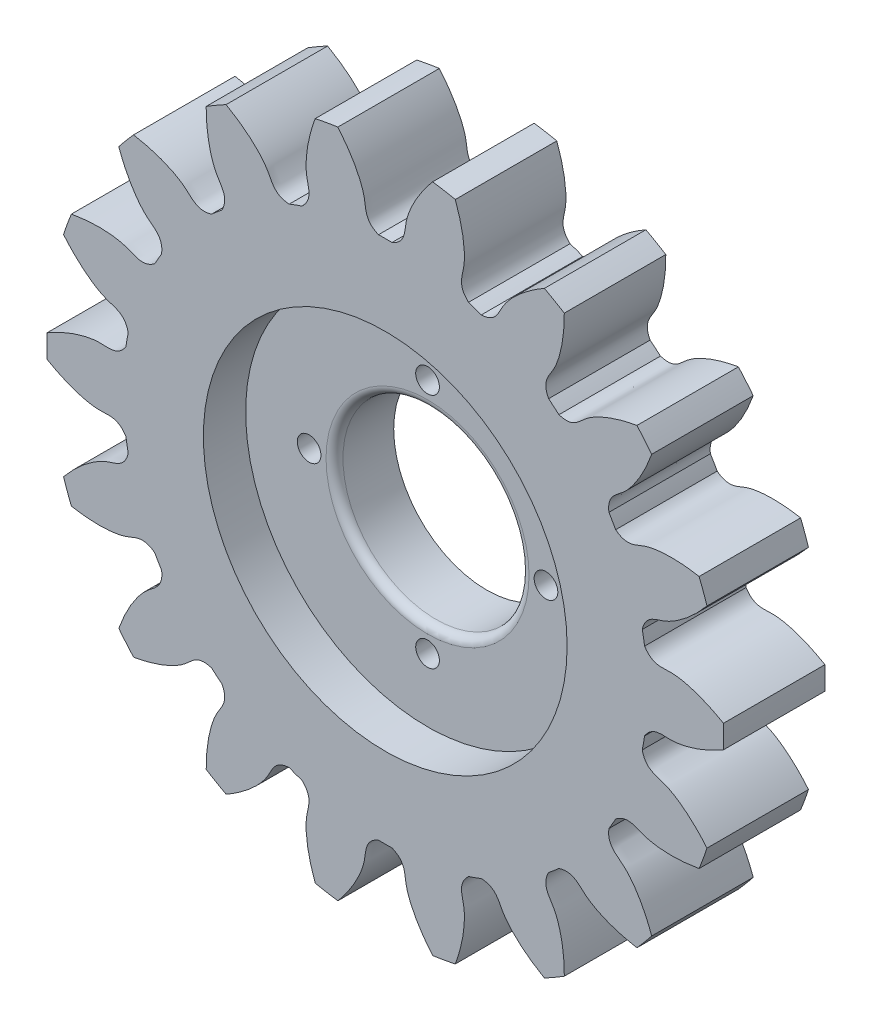
SolidWorks part; units mm, degrees
ref_plane "前视基准面" through (0, 0, 0) normal (0, 0, 1) x (1, 0, 0)
ref_plane "上视基准面" through (0, 0, 0) normal (0, 1, 0) x (1, 0, 0)
ref_plane "右视基准面" through (0, 0, 0) normal (1, 0, 0) x (0, 0, -1)
sketch "草图1" plane through (0, 0, 0) normal (0, 0, 1) x (1, 0, 0)
  circle A0 centre (0, 0) radius 20
extrude "凸台-拉伸1" add sketch "草图1" along normal blind 5
ref_axis "基准轴1" through (0, 0, -0.25) along (0, 0, 1)
sketch "草图2" plane through (0, 0, 0) normal (0, 0, 1) x (1, 0, 0)
  line L0 (0, 0) -> (0, 20) construction
  circle A0 centre (0, 0) radius 20 construction
  arc A1 (0.3988, 15.4949) -> (-0.3988, 15.4949) centre (0, 0) ccw
  arc A2 (6.1971, 22.6134) -> (-6.1971, 22.6134) centre (0, 0) ccw
  spline S0 degree 3 poles (0.3988, 15.4949) (1.2302, 15.8374) (1.1256, 16.4774) (1.2637, 17.0852) (1.2775, 17.141) (1.2942, 17.2031) (1.314, 17.2713) (1.3373, 17.3456) (1.3641, 17.4258) (1.3948, 17.5118) (1.4296, 17.6035) (1.4688, 17.7008) (1.5126, 17.8035) (1.5611, 17.9115) (1.6148, 18.0246) (1.6737, 18.1427) (1.738, 18.2655) (1.8081, 18.393) (1.8841, 18.5249) (1.9662, 18.6611) (2.0547, 18.8013) (2.1496, 18.9453) (2.2513, 19.0931) (2.3598, 19.2442) (2.4753, 19.3986) (2.5981, 19.5559) (2.7283, 19.7161) (2.866, 19.8787) (3.0115, 20.0437) (3.1648, 20.2106) (3.326, 20.3794) (3.4954, 20.5497) (3.673, 20.7213) (3.859, 20.8939) (4.0534, 21.0673) (4.2564, 21.2412) (4.468, 21.4152) (4.6884, 21.5892) (4.9177, 21.7628) (5.1558, 21.9358) (5.4029, 22.1078) (5.7482, 22.3381) (6.0151, 22.5047) (6.1971, 22.6134) knots 0 0 0 0 0.187592 0.192996 0.199121 0.205966 0.213531 0.221818 0.230824 0.240552 0.250999 0.262168 0.274057 0.286666 0.299996 0.314047 0.328818 0.344309 0.360521 0.377454 0.395107 0.413481 0.432575 0.45239 0.472926 0.494181 0.516158 0.538855 0.562272 0.58641 0.611269 0.636848 0.663148 0.690168 0.717909 0.74637 0.775552 0.805454 0.836077 0.867421 0.899485 0.932269 1 1 1 1
  spline S1 degree 3 poles (-0.3988, 15.4949) (-1.2302, 15.8374) (-1.1256, 16.4774) (-1.2637, 17.0852) (-1.2775, 17.141) (-1.2942, 17.2031) (-1.314, 17.2713) (-1.3373, 17.3456) (-1.3641, 17.4258) (-1.3948, 17.5118) (-1.4296, 17.6035) (-1.4688, 17.7008) (-1.5126, 17.8035) (-1.5611, 17.9115) (-1.6148, 18.0246) (-1.6737, 18.1427) (-1.738, 18.2655) (-1.8081, 18.393) (-1.8841, 18.5249) (-1.9662, 18.6611) (-2.0547, 18.8013) (-2.1496, 18.9453) (-2.2513, 19.0931) (-2.3598, 19.2442) (-2.4753, 19.3986) (-2.5981, 19.5559) (-2.7283, 19.7161) (-2.866, 19.8787) (-3.0115, 20.0437) (-3.1648, 20.2106) (-3.326, 20.3794) (-3.4954, 20.5497) (-3.673, 20.7213) (-3.859, 20.8939) (-4.0534, 21.0673) (-4.2564, 21.2412) (-4.468, 21.4152) (-4.6884, 21.5892) (-4.9177, 21.7628) (-5.1558, 21.9358) (-5.4029, 22.1078) (-5.7482, 22.3381) (-6.0151, 22.5047) (-6.1971, 22.6134) knots 0 0 0 0 0.187592 0.192996 0.199121 0.205966 0.213531 0.221818 0.230824 0.240552 0.250999 0.262168 0.274057 0.286666 0.299996 0.314047 0.328818 0.344309 0.360521 0.377454 0.395107 0.413481 0.432575 0.45239 0.472926 0.494181 0.516158 0.538855 0.562272 0.58641 0.611269 0.636848 0.663148 0.690168 0.717909 0.74637 0.775552 0.805454 0.836077 0.867421 0.899485 0.932269 1 1 1 1
extrude "切除-拉伸1" cut sketch "草图2" along normal through all
pattern_circular "阵列(圆周)1" count 18 every 20 about axis through (0, 0, -0.25) along (0, 0, 1) of "切除-拉伸1"
sketch "草图3" plane through (0, 0, 0) normal (0, 0, 1) x (1, 0, 0)
  circle A0 centre (0, 0) radius 18 construction
  dimension "Dn" = 36
sketch "草图4" plane through (0, 0, 5) normal (0, 0, 1) x (1, 0, 0)
  circle A0 centre (0, 0) radius 10.75
  dimension "D1" = 21.5
extrude "切除-拉伸2" cut sketch "草图4" against normal blind 2.5
sketch "草图5" plane through (0, 0, 2.5) normal (0, 0, 1) x (1, 0, 0)
  circle A0 centre (0, 0) radius 5.5
  dimension "D1" = 11
extrude "切除-拉伸3" cut sketch "草图5" against normal blind 12.5
sketch "草图7" plane through (0, 0, 0) normal (0, 0, -1) x (-1, 0, 0)
  circle A0 centre (0, 0) radius 5.5 construction
  circle A1 centre (0, 0) radius 5.5
  arc A36 (5.6743, 14.424) -> (4.9248, 14.6968) centre (0, 0) ccw
  arc A37 (4.14, 19.5668) -> (2.802, 19.8028) centre (0, 0) ccw
  arc A38 (0.3988, 15.4949) -> (-0.3988, 15.4949) centre (0, 0) ccw
  arc A39 (-2.802, 19.8028) -> (-4.14, 19.5668) centre (0, 0) ccw
  arc A40 (-4.9248, 14.6968) -> (-5.6743, 14.424) centre (0, 0) ccw
  arc A41 (-9.4059, 17.6502) -> (-10.5825, 16.9709) centre (0, 0) ccw
  arc A42 (-9.6544, 12.1261) -> (-10.2654, 11.6134) centre (0, 0) ccw
  arc A43 (-14.8754, 13.3687) -> (-15.7487, 12.3279) centre (0, 0) ccw
  arc A44 (-13.2195, 8.0928) -> (-13.6184, 7.4021) centre (0, 0) ccw
  arc A45 (-18.5507, 7.4748) -> (-19.0153, 6.1981) centre (0, 0) ccw
  arc A46 (-15.1902, 3.0834) -> (-15.3287, 2.2979) centre (0, 0) ccw
  arc A47 (-19.9885, 0.6793) -> (-19.9885, -0.6793) centre (0, 0) ccw
  arc A48 (-15.3287, -2.2979) -> (-15.1902, -3.0834) centre (0, 0) ccw
  arc A49 (-19.0153, -6.1981) -> (-18.5507, -7.4748) centre (0, 0) ccw
  arc A50 (-13.6184, -7.4021) -> (-13.2195, -8.0928) centre (0, 0) ccw
  arc A51 (-15.7487, -12.3279) -> (-14.8754, -13.3687) centre (0, 0) ccw
  arc A52 (-10.2654, -11.6134) -> (-9.6544, -12.1261) centre (0, 0) ccw
  arc A53 (-10.5825, -16.9709) -> (-9.4059, -17.6502) centre (0, 0) ccw
  arc A54 (-5.6743, -14.424) -> (-4.9248, -14.6968) centre (0, 0) ccw
  arc A55 (-4.14, -19.5668) -> (-2.802, -19.8028) centre (0, 0) ccw
  arc A56 (-0.3988, -15.4949) -> (0.3988, -15.4949) centre (0, 0) ccw
  arc A57 (2.802, -19.8028) -> (4.14, -19.5668) centre (0, 0) ccw
  arc A58 (4.9248, -14.6968) -> (5.6743, -14.424) centre (0, 0) ccw
  arc A59 (9.4059, -17.6502) -> (10.5825, -16.9709) centre (0, 0) ccw
  arc A60 (9.6544, -12.1261) -> (10.2654, -11.6134) centre (0, 0) ccw
  arc A61 (14.8754, -13.3687) -> (15.7487, -12.3279) centre (0, 0) ccw
  arc A62 (13.2195, -8.0928) -> (13.6184, -7.4021) centre (0, 0) ccw
  arc A63 (18.5507, -7.4748) -> (19.0153, -6.1981) centre (0, 0) ccw
  arc A64 (15.1902, -3.0834) -> (15.3287, -2.2979) centre (0, 0) ccw
  arc A65 (19.9885, -0.6793) -> (19.9885, 0.6793) centre (0, 0) ccw
  arc A66 (15.3287, 2.2979) -> (15.1902, 3.0834) centre (0, 0) ccw
  arc A67 (19.0153, 6.1981) -> (18.5507, 7.4748) centre (0, 0) ccw
  arc A68 (13.6184, 7.4021) -> (13.2195, 8.0928) centre (0, 0) ccw
  arc A69 (15.7487, 12.3279) -> (14.8754, 13.3687) centre (0, 0) ccw
  arc A70 (10.2654, 11.6134) -> (9.6544, 12.1261) centre (0, 0) ccw
  arc A71 (10.5825, 16.9709) -> (9.4059, 17.6502) centre (0, 0) ccw
  arc A72 (5.6743, 14.424) -> (4.9248, 14.6968) centre (0, 0) ccw
  arc A73 (4.14, 19.5668) -> (2.802, 19.8028) centre (0, 0) ccw
  arc A74 (0.3988, 15.4949) -> (-0.3988, 15.4949) centre (0, 0) ccw
  arc A75 (-2.802, 19.8028) -> (-4.14, 19.5668) centre (0, 0) ccw
  arc A76 (-4.9248, 14.6968) -> (-5.6743, 14.424) centre (0, 0) ccw
  arc A77 (-9.4059, 17.6502) -> (-10.5825, 16.9709) centre (0, 0) ccw
  arc A78 (-9.6544, 12.1261) -> (-10.2654, 11.6134) centre (0, 0) ccw
  arc A79 (-14.8754, 13.3687) -> (-15.7487, 12.3279) centre (0, 0) ccw
  arc A80 (-13.2195, 8.0928) -> (-13.6184, 7.4021) centre (0, 0) ccw
  arc A81 (-18.5507, 7.4748) -> (-19.0153, 6.1981) centre (0, 0) ccw
  arc A82 (-15.1902, 3.0834) -> (-15.3287, 2.2979) centre (0, 0) ccw
  arc A83 (-19.9885, 0.6793) -> (-19.9885, -0.6793) centre (0, 0) ccw
  arc A84 (-15.3287, -2.2979) -> (-15.1902, -3.0834) centre (0, 0) ccw
  arc A85 (-19.0153, -6.1981) -> (-18.5507, -7.4748) centre (0, 0) ccw
  arc A86 (-13.6184, -7.4021) -> (-13.2195, -8.0928) centre (0, 0) ccw
  arc A87 (-15.7487, -12.3279) -> (-14.8754, -13.3687) centre (0, 0) ccw
  arc A88 (-10.2654, -11.6134) -> (-9.6544, -12.1261) centre (0, 0) ccw
  arc A89 (-10.5825, -16.9709) -> (-9.4059, -17.6502) centre (0, 0) ccw
  arc A90 (-5.6743, -14.424) -> (-4.9248, -14.6968) centre (0, 0) ccw
  arc A91 (-4.14, -19.5668) -> (-2.802, -19.8028) centre (0, 0) ccw
  arc A92 (-0.3988, -15.4949) -> (0.3988, -15.4949) centre (0, 0) ccw
  arc A93 (2.802, -19.8028) -> (4.14, -19.5668) centre (0, 0) ccw
  arc A94 (4.9248, -14.6968) -> (5.6743, -14.424) centre (0, 0) ccw
  arc A95 (9.4059, -17.6502) -> (10.5825, -16.9709) centre (0, 0) ccw
  arc A96 (9.6544, -12.1261) -> (10.2654, -11.6134) centre (0, 0) ccw
  arc A97 (14.8754, -13.3687) -> (15.7487, -12.3279) centre (0, 0) ccw
  arc A98 (13.2195, -8.0928) -> (13.6184, -7.4021) centre (0, 0) ccw
  arc A99 (18.5507, -7.4748) -> (19.0153, -6.1981) centre (0, 0) ccw
  arc A100 (15.1902, -3.0834) -> (15.3287, -2.2979) centre (0, 0) ccw
  arc A101 (19.9885, -0.6793) -> (19.9885, 0.6793) centre (0, 0) ccw
  arc A102 (15.3287, 2.2979) -> (15.1902, 3.0834) centre (0, 0) ccw
  arc A103 (19.0153, 6.1981) -> (18.5507, 7.4748) centre (0, 0) ccw
  arc A104 (13.6184, 7.4021) -> (13.2195, 8.0928) centre (0, 0) ccw
  arc A105 (15.7487, 12.3279) -> (14.8754, 13.3687) centre (0, 0) ccw
  arc A106 (10.2654, 11.6134) -> (9.6544, 12.1261) centre (0, 0) ccw
  arc A107 (10.5825, 16.9709) -> (9.4059, 17.6502) centre (0, 0) ccw
  spline S36 degree 3 poles (-1821.1563, 823.0655) (138.0406, -70.6947) (34.3771, 34.3484) (8.6502, 17.177) (8.3656, 16.9701) (8.1106, 16.7688) (7.8845, 16.5751) (7.7151, 16.4178) (7.5666, 16.2712) (7.4606, 16.1603) (7.3642, 16.0529) (7.3001, 15.9787) (7.2418, 15.9083) (7.1891, 15.8421) (7.1419, 15.7803) (7.0886, 15.7075) (7.0425, 15.6406) (3.1814, 9.6493) (27.7855, -14.1214) (-1623.8886, 1173.6915) knots -9.275364 -9.275364 -9.275364 -9.275364 0.527074 0.567425 0.604893 0.639479 0.671182 0.700004 0.713334 0.737832 0.749001 0.759448 0.769176 0.778182 0.786469 0.794034 0.807004 0.812408 3.071148 3.071148 3.071148 3.071148 only from (9.4059, 17.6502) to (5.6743, 14.424)
  spline S37 degree 3 poles (1998.3999, -144.7152) (-30.3619, 7.0426) (3.7654, 9.4367) (4.6587, 16.5083) (4.6664, 16.5891) (4.6723, 16.6791) (4.6759, 16.7569) (4.6781, 16.8414) (4.6789, 16.9677) (4.6746, 17.1425) (4.6597, 17.3721) (4.6329, 17.6278) (4.5921, 17.9091) (4.535, 18.2151) (4.4598, 18.545) (4.3644, 18.8978) (-5.0832, 49.0019) (-152.7401, 32.5697) (1924.3252, -539.3464) knots -2.071146 -2.071146 -2.071146 -2.071146 0.187592 0.192996 0.205966 0.213531 0.221818 0.230824 0.240552 0.262168 0.286666 0.314047 0.344309 0.377454 0.413481 0.45239 0.494181 10.492028 10.492028 10.492028 10.492028 only from (4.9248, 14.6968) to (4.14, 19.5668)
  spline S38 degree 3 poles (-1992.8321, 150.5565) (153.8948, -19.2186) (20.556, 44.0346) (2.2536, 19.0996) (2.0569, 18.8079) (1.8862, 18.5315) (1.74, 18.2722) (1.6346, 18.0664) (1.5452, 17.8779) (1.4835, 17.7374) (1.4296, 17.6035) (1.3948, 17.5118) (1.3641, 17.4258) (1.3373, 17.3456) (1.314, 17.2713) (1.2889, 17.1847) (1.2684, 17.1061) (-0.3107, 10.1555) (30.9397, -3.7665) (-1927.3823, 547.5066) knots -9.275364 -9.275364 -9.275364 -9.275364 0.527074 0.567425 0.604893 0.639479 0.671182 0.700004 0.713334 0.737832 0.749001 0.759448 0.769176 0.778182 0.786469 0.794034 0.807004 0.812408 3.071148 3.071148 3.071148 3.071148 only from (2.802, 19.8028) to (0.3988, 15.4949)
  spline S39 degree 3 poles (1927.3772, 547.5052) (-30.9396, -3.7665) (0.3107, 10.1555) (-1.2684, 17.1061) (-1.2889, 17.1847) (-1.314, 17.2713) (-1.3373, 17.3456) (-1.3641, 17.4258) (-1.4066, 17.5447) (-1.4704, 17.7075) (-1.5629, 17.9181) (-1.6755, 18.1493) (-1.8102, 18.3996) (-1.9684, 18.6677) (-2.1519, 18.9519) (-2.3622, 19.2508) (-21.5363, 44.3082) (-154.6683, -21.6347) (1992.7415, 151.3382) knots -2.071146 -2.071146 -2.071146 -2.071146 0.187592 0.192996 0.205966 0.213531 0.221818 0.230824 0.240552 0.262168 0.286666 0.314047 0.344309 0.377454 0.413481 0.45239 0.494181 10.492028 10.492028 10.492028 10.492028 only from (-0.3988, 15.4949) to (-2.802, 19.8028)
  spline S40 degree 3 poles (-1924.143, -540.1119) (151.1869, 34.5755) (4.2556, 48.4096) (-4.4147, 18.7186) (-4.4998, 18.3771) (-4.5657, 18.0591) (-4.6144, 17.7653) (-4.6431, 17.5359) (-4.6626, 17.3282) (-4.6725, 17.1751) (-4.6774, 17.0309) (-4.6787, 16.9328) (-4.6781, 16.8414) (-4.6759, 16.7569) (-4.6723, 16.6791) (-4.6664, 16.5891) (-4.6587, 16.5083) (-3.7654, 9.4367) (30.362, 7.0426) (-1998.4052, -144.7156) knots -9.275364 -9.275364 -9.275364 -9.275364 0.527074 0.567425 0.604893 0.639479 0.671182 0.700004 0.713334 0.737832 0.749001 0.759448 0.769176 0.778182 0.786469 0.794034 0.807004 0.812408 3.071148 3.071148 3.071148 3.071148 only from (-4.14, 19.5668) to (-4.9248, 14.6968)
  spline S41 degree 3 poles (1623.8843, 1173.6884) (-27.7855, -14.1213) (-3.1814, 9.6493) (-7.0425, 15.6406) (-7.0886, 15.7075) (-7.1419, 15.7803) (-7.1891, 15.8421) (-7.2418, 15.9083) (-7.3224, 16.0056) (-7.438, 16.1367) (-7.597, 16.303) (-7.7819, 16.4817) (-7.994, 16.6709) (-8.2344, 16.8686) (-8.5041, 17.073) (-8.8039, 17.2819) (-35.3918, 34.2702) (-137.9411, -73.2297) (1820.8038, 823.7691) knots -2.071146 -2.071146 -2.071146 -2.071146 0.187592 0.192996 0.205966 0.213531 0.221818 0.230824 0.240552 0.262168 0.286666 0.314047 0.344309 0.377454 0.413481 0.45239 0.494181 10.492028 10.492028 10.492028 10.492028 only from (-5.6743, 14.424) to (-9.4059, 17.6502)
  spline S42 degree 3 poles (-1623.3738, -1165.6349) (130.2437, 84.1993) (-12.558, 46.9456) (-10.5506, 16.0798) (-10.5138, 15.7298) (-10.4669, 15.4084) (-10.4122, 15.1157) (-10.3607, 14.8903) (-10.308, 14.6885) (-10.2649, 14.5413) (-10.2202, 14.404) (-10.1879, 14.3114) (-10.1561, 14.2257) (-10.1251, 14.1471) (-10.0952, 14.0752) (-10.0588, 13.9927) (-10.0239, 13.9193) (-6.7658, 7.5798) (26.1222, 17.0023) (-1828.391, -819.483) knots -9.275364 -9.275364 -9.275364 -9.275364 0.527074 0.567425 0.604893 0.639479 0.671182 0.700004 0.713334 0.737832 0.749001 0.759448 0.769176 0.778182 0.786469 0.794034 0.807004 0.812408 3.071148 3.071148 3.071148 3.071148 only from (-10.5825, 16.9709) to (-9.6544, 12.1261)
  spline S43 degree 3 poles (1124.527, 1658.3075) (-21.28, -22.7729) (-6.2898, 7.9793) (-11.9672, 12.2887) (-12.0334, 12.3358) (-12.1084, 12.3859) (-12.1739, 12.4279) (-12.246, 12.4721) (-12.355, 12.5359) (-12.5085, 12.6196) (-12.7148, 12.7215) (-12.9497, 12.8262) (-13.2137, 12.9314) (-13.5072, 13.035) (-13.8306, 13.1348) (-14.1837, 13.2285) (-44.9785, 20.0988) (-104.5762, -115.992) (1429.2502, 1396.8413) knots -2.071146 -2.071146 -2.071146 -2.071146 0.187592 0.192996 0.205966 0.213531 0.221818 0.230824 0.240552 0.262168 0.286666 0.314047 0.344309 0.377454 0.413481 0.45239 0.494181 10.492028 10.492028 10.492028 10.492028 only from (-10.2654, 11.6134) to (-14.8754, 13.3687)
  spline S44 degree 3 poles (-1126.8018, -1650.565) (93.5912, 123.6675) (-27.857, 39.8193) (-15.414, 11.5015) (-15.2596, 11.1853) (-15.1057, 10.8993) (-14.9542, 10.643) (-14.8287, 10.4488) (-14.7101, 10.2771) (-14.6193, 10.1535) (-14.5303, 10.0399) (-14.4683, 9.9638) (-14.4091, 9.8942) (-14.3531, 9.8309) (-14.3004, 9.7737) (-14.2379, 9.7085) (-14.1801, 9.6515) (-8.9503, 4.8086) (18.7317, 24.9113) (-1437.8458, -1395.4087) knots -9.275364 -9.275364 -9.275364 -9.275364 0.527074 0.567425 0.604893 0.639479 0.671182 0.700004 0.713334 0.737832 0.749001 0.759448 0.769176 0.778182 0.786469 0.794034 0.807004 0.812408 3.071148 3.071148 3.071148 3.071148 only from (-15.7487, 12.3279) to (-13.2195, 8.0928)
  spline S45 degree 3 poles (489.5352, 1942.9102) (-12.2079, -28.6777) (-8.6395, 5.3468) (-15.4485, 7.4546) (-15.5268, 7.4761) (-15.6144, 7.4977) (-15.6903, 7.5147) (-15.7732, 7.5315) (-15.8975, 7.5543) (-16.0703, 7.5803) (-16.299, 7.6056) (-16.5555, 7.6236) (-16.8396, 7.6322) (-17.1509, 7.6291) (-17.4888, 7.6123) (-17.8528, 7.5796) (-49.1401, 3.5031) (-58.5979, -144.764) (865.308, 1801.4338) knots -2.071146 -2.071146 -2.071146 -2.071146 0.187592 0.192996 0.205966 0.213531 0.221818 0.230824 0.240552 0.262168 0.286666 0.314047 0.344309 0.377454 0.413481 0.45239 0.494181 10.492028 10.492028 10.492028 10.492028 only from (-13.6184, 7.4021) to (-18.5507, 7.4748)
  spline S46 degree 3 poles (-494.3208, -1936.4127) (45.6502, 148.2195) (-39.7961, 27.8903) (-18.4181, 5.536) (-18.165, 5.2916) (-17.9224, 5.0755) (-17.6924, 4.8865) (-17.5081, 4.7469) (-17.3379, 4.6262) (-17.2103, 4.5411) (-17.0878, 4.4647) (-17.0036, 4.4145) (-16.9242, 4.3693) (-16.8498, 4.329) (-16.7807, 4.2932) (-16.6998, 4.2534) (-16.6259, 4.2196) (-10.0551, 1.4575) (9.0819, 29.8156) (-873.8752, -1803.0275) knots -9.275364 -9.275364 -9.275364 -9.275364 0.527074 0.567425 0.604893 0.639479 0.671182 0.700004 0.713334 0.737832 0.749001 0.759448 0.769176 0.778182 0.786469 0.794034 0.807004 0.812408 3.071148 3.071148 3.071148 3.071148 only from (-19.0153, 6.1981) to (-15.1902, 3.0834)
  spline S47 degree 3 poles (-204.5019, 1993.1693) (-1.6633, -31.1236) (-9.9472, 2.0695) (-17.0665, 1.7213) (-17.1474, 1.7148) (-17.2371, 1.705) (-17.3143, 1.6951) (-17.3979, 1.6826) (-17.5224, 1.6614) (-17.6938, 1.6268) (-17.9173, 1.5723) (-18.1645, 1.5015) (-18.4344, 1.4124) (-18.7259, 1.3031) (-19.0377, 1.1717) (-19.3685, 1.0165) (-47.3748, -13.5151) (-5.5518, -156.0753) (196.9969, 1988.7469) knots -2.071146 -2.071146 -2.071146 -2.071146 0.187592 0.192996 0.205966 0.213531 0.221818 0.230824 0.240552 0.262168 0.286666 0.314047 0.344309 0.377454 0.413481 0.45239 0.494181 10.492028 10.492028 10.492028 10.492028 only from (-15.3287, 2.2979) to (-19.9885, 0.6793)
  spline S48 degree 3 poles (197.7825, -1988.7004) (-7.7969, 154.8941) (-46.9351, 12.5972) (-19.2008, -1.0972) (-18.8793, -1.2403) (-18.5775, -1.3604) (-18.2967, -1.4594) (-18.0758, -1.5275) (-17.8746, -1.5827) (-17.7256, -1.6191) (-17.5843, -1.6489) (-17.488, -1.6673) (-17.3979, -1.6826) (-17.3143, -1.6951) (-17.2371, -1.705) (-17.1474, -1.7148) (-17.0665, -1.7213) (-9.9472, -2.0695) (-1.6633, 31.1237) (-204.5024, -1993.1745) knots -9.275364 -9.275364 -9.275364 -9.275364 0.527074 0.567425 0.604893 0.639479 0.671182 0.700004 0.713334 0.737832 0.749001 0.759448 0.769176 0.778182 0.786469 0.794034 0.807004 0.812408 3.071148 3.071148 3.071148 3.071148 only from (-19.9885, -0.6793) to (-15.3287, -2.2979)
  spline S49 degree 3 poles (-873.8729, 1803.0227) (9.0819, -29.8155) (-10.0551, -1.4575) (-16.6259, -4.2196) (-16.6998, -4.2534) (-16.7807, -4.2932) (-16.8498, -4.329) (-16.9242, -4.3693) (-17.0339, -4.4318) (-17.1831, -4.5229) (-17.3745, -4.6506) (-17.5826, -4.8017) (-17.8058, -4.9777) (-18.0423, -5.1801) (-18.2903, -5.4102) (-18.5481, -5.6692) (-39.8953, -28.9031) (48.1639, -148.5617) (-495.0749, 1936.1877) knots -2.071146 -2.071146 -2.071146 -2.071146 0.187592 0.192996 0.205966 0.213531 0.221818 0.230824 0.240552 0.262168 0.286666 0.314047 0.344309 0.377454 0.413481 0.45239 0.494181 10.492028 10.492028 10.492028 10.492028 only from (-15.1902, -3.0834) to (-19.0153, -6.1981)
  spline S50 degree 3 poles (866.0303, -1801.1215) (-60.3036, 142.8861) (-48.4131, -4.2152) (-17.6676, -7.5981) (-17.3166, -7.6226) (-16.9919, -7.6322) (-16.6941, -7.6292) (-16.4632, -7.6176) (-16.2553, -7.6008) (-16.1028, -7.5839) (-15.9599, -7.5637) (-15.8631, -7.548) (-15.7732, -7.5315) (-15.6903, -7.5147) (-15.6144, -7.4977) (-15.5268, -7.4761) (-15.4485, -7.4546) (-8.6395, -5.3468) (-12.2079, 28.6778) (489.5365, -1942.9153) knots -9.275364 -9.275364 -9.275364 -9.275364 0.527074 0.567425 0.604893 0.639479 0.671182 0.700004 0.713334 0.737832 0.749001 0.759448 0.769176 0.778182 0.786469 0.794034 0.807004 0.812408 3.071148 3.071148 3.071148 3.071148 only from (-18.5507, -7.4748) to (-13.6184, -7.4021)
  spline S51 degree 3 poles (-1437.842, 1395.405) (18.7317, -24.9112) (-8.9503, -4.8086) (-14.1801, -9.6515) (-14.2379, -9.7085) (-14.3004, -9.7737) (-14.3531, -9.8309) (-14.4091, -9.8942) (-14.4909, -9.9905) (-14.5999, -10.1271) (-14.7361, -10.3126) (-14.88, -10.5257) (-15.0295, -10.7675) (-15.1825, -11.0385) (-15.3369, -11.3396) (-15.4906, -11.6712) (-27.6039, -40.805) (96.0703, -123.1293) (-1127.4334, 1650.0957) knots -2.071146 -2.071146 -2.071146 -2.071146 0.187592 0.192996 0.205966 0.213531 0.221818 0.230824 0.240552 0.262168 0.286666 0.314047 0.344309 0.377454 0.413481 0.45239 0.494181 10.492028 10.492028 10.492028 10.492028 only from (-13.2195, -8.0928) to (-15.7487, -12.3279)
  spline S52 degree 3 poles (1429.8221, -1396.3007) (-105.5367, 113.644) (-44.0517, -20.5193) (-14.0034, -13.1826) (-13.6652, -13.0855) (-13.3568, -12.9835) (-13.078, -12.8788) (-12.865, -12.789) (-12.6754, -12.702) (-12.5378, -12.6341) (-12.4105, -12.5661) (-12.3248, -12.5183) (-12.246, -12.4721) (-12.1739, -12.4279) (-12.1084, -12.3859) (-12.0334, -12.3358) (-11.9672, -12.2887) (-6.2898, -7.9793) (-21.2801, 22.773) (1124.53, -1658.3119) knots -9.275364 -9.275364 -9.275364 -9.275364 0.527074 0.567425 0.604893 0.639479 0.671182 0.700004 0.713334 0.737832 0.749001 0.759448 0.769176 0.778182 0.786469 0.794034 0.807004 0.812408 3.071148 3.071148 3.071148 3.071148 only from (-14.8754, -13.3687) to (-10.2654, -11.6134)
  spline S53 degree 3 poles (-1828.3862, 819.4808) (26.1222, -17.0023) (-6.7659, -7.5798) (-10.0239, -13.9193) (-10.0588, -13.9927) (-10.0952, -14.0752) (-10.1251, -14.1471) (-10.1561, -14.2257) (-10.2, -14.3442) (-10.2558, -14.5099) (-10.3203, -14.7307) (-10.3826, -14.9802) (-10.4404, -15.2585) (-10.4915, -15.5655) (-10.5336, -15.9013) (-10.5646, -16.2654) (-11.983, -47.7853) (132.3893, -82.8457) (-1623.8068, 1164.9778) knots -2.071146 -2.071146 -2.071146 -2.071146 0.187592 0.192996 0.205966 0.213531 0.221818 0.230824 0.240552 0.262168 0.286666 0.314047 0.344309 0.377454 0.413481 0.45239 0.494181 10.492028 10.492028 10.492028 10.492028 only from (-9.6544, -12.1261) to (-10.5825, -16.9709)
  spline S54 degree 3 poles (1821.1563, -823.0655) (-138.0406, 70.6947) (-34.3771, -34.3484) (-8.6502, -17.177) (-8.3656, -16.9701) (-8.1106, -16.7688) (-7.8845, -16.5751) (-7.7151, -16.4178) (-7.5666, -16.2712) (-7.4606, -16.1603) (-7.3642, -16.0529) (-7.3001, -15.9787) (-7.2418, -15.9083) (-7.1891, -15.8421) (-7.1419, -15.7803) (-7.0886, -15.7075) (-7.0425, -15.6406) (-3.1814, -9.6493) (-27.7855, 14.1214) (1623.8886, -1173.6915) knots -9.275364 -9.275364 -9.275364 -9.275364 0.527074 0.567425 0.604893 0.639479 0.671182 0.700004 0.713334 0.737832 0.749001 0.759448 0.769176 0.778182 0.786469 0.794034 0.807004 0.812408 3.071148 3.071148 3.071148 3.071148 only from (-9.4059, -17.6502) to (-5.6743, -14.424)
  spline S55 degree 3 poles (-1998.3999, 144.7152) (30.3619, -7.0426) (-3.7654, -9.4367) (-4.6587, -16.5083) (-4.6664, -16.5891) (-4.6723, -16.6791) (-4.6759, -16.7569) (-4.6781, -16.8414) (-4.6789, -16.9677) (-4.6746, -17.1425) (-4.6597, -17.3721) (-4.6329, -17.6278) (-4.5921, -17.9091) (-4.535, -18.2151) (-4.4598, -18.545) (-4.3644, -18.8978) (5.0832, -49.0019) (152.7401, -32.5697) (-1924.3252, 539.3464) knots -2.071146 -2.071146 -2.071146 -2.071146 0.187592 0.192996 0.205966 0.213531 0.221818 0.230824 0.240552 0.262168 0.286666 0.314047 0.344309 0.377454 0.413481 0.45239 0.494181 10.492028 10.492028 10.492028 10.492028 only from (-4.9248, -14.6968) to (-4.14, -19.5668)
  spline S56 degree 3 poles (1992.8321, -150.5565) (-153.8948, 19.2186) (-20.556, -44.0346) (-2.2536, -19.0996) (-2.0569, -18.8079) (-1.8862, -18.5315) (-1.74, -18.2722) (-1.6346, -18.0664) (-1.5452, -17.8779) (-1.4835, -17.7374) (-1.4296, -17.6035) (-1.3948, -17.5118) (-1.3641, -17.4258) (-1.3373, -17.3456) (-1.314, -17.2713) (-1.2889, -17.1847) (-1.2684, -17.1061) (0.3107, -10.1555) (-30.9397, 3.7665) (1927.3823, -547.5066) knots -9.275364 -9.275364 -9.275364 -9.275364 0.527074 0.567425 0.604893 0.639479 0.671182 0.700004 0.713334 0.737832 0.749001 0.759448 0.769176 0.778182 0.786469 0.794034 0.807004 0.812408 3.071148 3.071148 3.071148 3.071148 only from (-2.802, -19.8028) to (-0.3988, -15.4949)
  spline S57 degree 3 poles (-1927.3772, -547.5052) (30.9396, 3.7665) (-0.3107, -10.1555) (1.2684, -17.1061) (1.2889, -17.1847) (1.314, -17.2713) (1.3373, -17.3456) (1.3641, -17.4258) (1.4066, -17.5447) (1.4704, -17.7075) (1.5629, -17.9181) (1.6755, -18.1493) (1.8102, -18.3996) (1.9684, -18.6677) (2.1519, -18.9519) (2.3622, -19.2508) (21.5363, -44.3082) (154.6683, 21.6347) (-1992.7415, -151.3382) knots -2.071146 -2.071146 -2.071146 -2.071146 0.187592 0.192996 0.205966 0.213531 0.221818 0.230824 0.240552 0.262168 0.286666 0.314047 0.344309 0.377454 0.413481 0.45239 0.494181 10.492028 10.492028 10.492028 10.492028 only from (0.3988, -15.4949) to (2.802, -19.8028)
  spline S58 degree 3 poles (1924.143, 540.1119) (-151.1869, -34.5755) (-4.2556, -48.4096) (4.4147, -18.7186) (4.4998, -18.3771) (4.5657, -18.0591) (4.6144, -17.7653) (4.6431, -17.5359) (4.6626, -17.3282) (4.6725, -17.1751) (4.6774, -17.0309) (4.6787, -16.9328) (4.6781, -16.8414) (4.6759, -16.7569) (4.6723, -16.6791) (4.6664, -16.5891) (4.6587, -16.5083) (3.7654, -9.4367) (-30.362, -7.0426) (1998.4052, 144.7156) knots -9.275364 -9.275364 -9.275364 -9.275364 0.527074 0.567425 0.604893 0.639479 0.671182 0.700004 0.713334 0.737832 0.749001 0.759448 0.769176 0.778182 0.786469 0.794034 0.807004 0.812408 3.071148 3.071148 3.071148 3.071148 only from (4.14, -19.5668) to (4.9248, -14.6968)
  spline S59 degree 3 poles (-1623.8843, -1173.6884) (27.7855, 14.1213) (3.1814, -9.6493) (7.0425, -15.6406) (7.0886, -15.7075) (7.1419, -15.7803) (7.1891, -15.8421) (7.2418, -15.9083) (7.3224, -16.0056) (7.438, -16.1367) (7.597, -16.303) (7.7819, -16.4817) (7.994, -16.6709) (8.2344, -16.8686) (8.5041, -17.073) (8.8039, -17.2819) (35.3918, -34.2702) (137.9411, 73.2297) (-1820.8038, -823.7691) knots -2.071146 -2.071146 -2.071146 -2.071146 0.187592 0.192996 0.205966 0.213531 0.221818 0.230824 0.240552 0.262168 0.286666 0.314047 0.344309 0.377454 0.413481 0.45239 0.494181 10.492028 10.492028 10.492028 10.492028 only from (5.6743, -14.424) to (9.4059, -17.6502)
  spline S60 degree 3 poles (1623.3738, 1165.6349) (-130.2437, -84.1993) (12.558, -46.9456) (10.5506, -16.0798) (10.5138, -15.7298) (10.4669, -15.4084) (10.4122, -15.1157) (10.3607, -14.8903) (10.308, -14.6885) (10.2649, -14.5413) (10.2202, -14.404) (10.1879, -14.3114) (10.1561, -14.2257) (10.1251, -14.1471) (10.0952, -14.0752) (10.0588, -13.9927) (10.0239, -13.9193) (6.7658, -7.5798) (-26.1222, -17.0023) (1828.391, 819.483) knots -9.275364 -9.275364 -9.275364 -9.275364 0.527074 0.567425 0.604893 0.639479 0.671182 0.700004 0.713334 0.737832 0.749001 0.759448 0.769176 0.778182 0.786469 0.794034 0.807004 0.812408 3.071148 3.071148 3.071148 3.071148 only from (10.5825, -16.9709) to (9.6544, -12.1261)
  spline S61 degree 3 poles (-1124.527, -1658.3075) (21.28, 22.7729) (6.2898, -7.9793) (11.9672, -12.2887) (12.0334, -12.3358) (12.1084, -12.3859) (12.1739, -12.4279) (12.246, -12.4721) (12.355, -12.5359) (12.5085, -12.6196) (12.7148, -12.7215) (12.9497, -12.8262) (13.2137, -12.9314) (13.5072, -13.035) (13.8306, -13.1348) (14.1837, -13.2285) (44.9785, -20.0988) (104.5762, 115.992) (-1429.2502, -1396.8413) knots -2.071146 -2.071146 -2.071146 -2.071146 0.187592 0.192996 0.205966 0.213531 0.221818 0.230824 0.240552 0.262168 0.286666 0.314047 0.344309 0.377454 0.413481 0.45239 0.494181 10.492028 10.492028 10.492028 10.492028 only from (10.2654, -11.6134) to (14.8754, -13.3687)
  spline S62 degree 3 poles (1126.8018, 1650.565) (-93.5912, -123.6675) (27.857, -39.8193) (15.414, -11.5015) (15.2596, -11.1853) (15.1057, -10.8993) (14.9542, -10.643) (14.8287, -10.4488) (14.7101, -10.2771) (14.6193, -10.1535) (14.5303, -10.0399) (14.4683, -9.9638) (14.4091, -9.8942) (14.3531, -9.8309) (14.3004, -9.7737) (14.2379, -9.7085) (14.1801, -9.6515) (8.9503, -4.8086) (-18.7317, -24.9113) (1437.8458, 1395.4087) knots -9.275364 -9.275364 -9.275364 -9.275364 0.527074 0.567425 0.604893 0.639479 0.671182 0.700004 0.713334 0.737832 0.749001 0.759448 0.769176 0.778182 0.786469 0.794034 0.807004 0.812408 3.071148 3.071148 3.071148 3.071148 only from (15.7487, -12.3279) to (13.2195, -8.0928)
  spline S63 degree 3 poles (-489.5352, -1942.9102) (12.2079, 28.6777) (8.6395, -5.3468) (15.4485, -7.4546) (15.5268, -7.4761) (15.6144, -7.4977) (15.6903, -7.5147) (15.7732, -7.5315) (15.8975, -7.5543) (16.0703, -7.5803) (16.299, -7.6056) (16.5555, -7.6236) (16.8396, -7.6322) (17.1509, -7.6291) (17.4888, -7.6123) (17.8528, -7.5796) (49.1401, -3.5031) (58.5979, 144.764) (-865.308, -1801.4338) knots -2.071146 -2.071146 -2.071146 -2.071146 0.187592 0.192996 0.205966 0.213531 0.221818 0.230824 0.240552 0.262168 0.286666 0.314047 0.344309 0.377454 0.413481 0.45239 0.494181 10.492028 10.492028 10.492028 10.492028 only from (13.6184, -7.4021) to (18.5507, -7.4748)
  spline S64 degree 3 poles (494.3208, 1936.4127) (-45.6502, -148.2195) (39.7961, -27.8903) (18.4181, -5.536) (18.165, -5.2916) (17.9224, -5.0755) (17.6924, -4.8865) (17.5081, -4.7469) (17.3379, -4.6262) (17.2103, -4.5411) (17.0878, -4.4647) (17.0036, -4.4145) (16.9242, -4.3693) (16.8498, -4.329) (16.7807, -4.2932) (16.6998, -4.2534) (16.6259, -4.2196) (10.0551, -1.4575) (-9.0819, -29.8156) (873.8752, 1803.0275) knots -9.275364 -9.275364 -9.275364 -9.275364 0.527074 0.567425 0.604893 0.639479 0.671182 0.700004 0.713334 0.737832 0.749001 0.759448 0.769176 0.778182 0.786469 0.794034 0.807004 0.812408 3.071148 3.071148 3.071148 3.071148 only from (19.0153, -6.1981) to (15.1902, -3.0834)
  spline S65 degree 3 poles (204.5019, -1993.1693) (1.6633, 31.1236) (9.9472, -2.0695) (17.0665, -1.7213) (17.1474, -1.7148) (17.2371, -1.705) (17.3143, -1.6951) (17.3979, -1.6826) (17.5224, -1.6614) (17.6938, -1.6268) (17.9173, -1.5723) (18.1645, -1.5015) (18.4344, -1.4124) (18.7259, -1.3031) (19.0377, -1.1717) (19.3685, -1.0165) (47.3748, 13.5151) (5.5518, 156.0753) (-196.9969, -1988.7469) knots -2.071146 -2.071146 -2.071146 -2.071146 0.187592 0.192996 0.205966 0.213531 0.221818 0.230824 0.240552 0.262168 0.286666 0.314047 0.344309 0.377454 0.413481 0.45239 0.494181 10.492028 10.492028 10.492028 10.492028 only from (15.3287, -2.2979) to (19.9885, -0.6793)
  spline S66 degree 3 poles (-197.7825, 1988.7004) (7.7969, -154.8941) (46.9351, -12.5972) (19.2008, 1.0972) (18.8793, 1.2403) (18.5775, 1.3604) (18.2967, 1.4594) (18.0758, 1.5275) (17.8746, 1.5827) (17.7256, 1.6191) (17.5843, 1.6489) (17.488, 1.6673) (17.3979, 1.6826) (17.3143, 1.6951) (17.2371, 1.705) (17.1474, 1.7148) (17.0665, 1.7213) (9.9472, 2.0695) (1.6633, -31.1237) (204.5024, 1993.1745) knots -9.275364 -9.275364 -9.275364 -9.275364 0.527074 0.567425 0.604893 0.639479 0.671182 0.700004 0.713334 0.737832 0.749001 0.759448 0.769176 0.778182 0.786469 0.794034 0.807004 0.812408 3.071148 3.071148 3.071148 3.071148 only from (19.9885, 0.6793) to (15.3287, 2.2979)
  spline S67 degree 3 poles (873.8729, -1803.0227) (-9.0819, 29.8155) (10.0551, 1.4575) (16.6259, 4.2196) (16.6998, 4.2534) (16.7807, 4.2932) (16.8498, 4.329) (16.9242, 4.3693) (17.0339, 4.4318) (17.1831, 4.5229) (17.3745, 4.6506) (17.5826, 4.8017) (17.8058, 4.9777) (18.0423, 5.1801) (18.2903, 5.4102) (18.5481, 5.6692) (39.8953, 28.9031) (-48.1639, 148.5617) (495.0749, -1936.1877) knots -2.071146 -2.071146 -2.071146 -2.071146 0.187592 0.192996 0.205966 0.213531 0.221818 0.230824 0.240552 0.262168 0.286666 0.314047 0.344309 0.377454 0.413481 0.45239 0.494181 10.492028 10.492028 10.492028 10.492028 only from (15.1902, 3.0834) to (19.0153, 6.1981)
  spline S68 degree 3 poles (-866.0303, 1801.1215) (60.3036, -142.8861) (48.4131, 4.2152) (17.6676, 7.5981) (17.3166, 7.6226) (16.9919, 7.6322) (16.6941, 7.6292) (16.4632, 7.6176) (16.2553, 7.6008) (16.1028, 7.5839) (15.9599, 7.5637) (15.8631, 7.548) (15.7732, 7.5315) (15.6903, 7.5147) (15.6144, 7.4977) (15.5268, 7.4761) (15.4485, 7.4546) (8.6395, 5.3468) (12.2079, -28.6778) (-489.5365, 1942.9153) knots -9.275364 -9.275364 -9.275364 -9.275364 0.527074 0.567425 0.604893 0.639479 0.671182 0.700004 0.713334 0.737832 0.749001 0.759448 0.769176 0.778182 0.786469 0.794034 0.807004 0.812408 3.071148 3.071148 3.071148 3.071148 only from (18.5507, 7.4748) to (13.6184, 7.4021)
  spline S69 degree 3 poles (1437.842, -1395.405) (-18.7317, 24.9112) (8.9503, 4.8086) (14.1801, 9.6515) (14.2379, 9.7085) (14.3004, 9.7737) (14.3531, 9.8309) (14.4091, 9.8942) (14.4909, 9.9905) (14.5999, 10.1271) (14.7361, 10.3126) (14.88, 10.5257) (15.0295, 10.7675) (15.1825, 11.0385) (15.3369, 11.3396) (15.4906, 11.6712) (27.6039, 40.805) (-96.0703, 123.1293) (1127.4334, -1650.0957) knots -2.071146 -2.071146 -2.071146 -2.071146 0.187592 0.192996 0.205966 0.213531 0.221818 0.230824 0.240552 0.262168 0.286666 0.314047 0.344309 0.377454 0.413481 0.45239 0.494181 10.492028 10.492028 10.492028 10.492028 only from (13.2195, 8.0928) to (15.7487, 12.3279)
  spline S70 degree 3 poles (-1429.8221, 1396.3007) (105.5367, -113.644) (44.0517, 20.5193) (14.0034, 13.1826) (13.6652, 13.0855) (13.3568, 12.9835) (13.078, 12.8788) (12.865, 12.789) (12.6754, 12.702) (12.5378, 12.6341) (12.4105, 12.5661) (12.3248, 12.5183) (12.246, 12.4721) (12.1739, 12.4279) (12.1084, 12.3859) (12.0334, 12.3358) (11.9672, 12.2887) (6.2898, 7.9793) (21.2801, -22.773) (-1124.53, 1658.3119) knots -9.275364 -9.275364 -9.275364 -9.275364 0.527074 0.567425 0.604893 0.639479 0.671182 0.700004 0.713334 0.737832 0.749001 0.759448 0.769176 0.778182 0.786469 0.794034 0.807004 0.812408 3.071148 3.071148 3.071148 3.071148 only from (14.8754, 13.3687) to (10.2654, 11.6134)
  spline S71 degree 3 poles (1828.3862, -819.4808) (-26.1222, 17.0023) (6.7659, 7.5798) (10.0239, 13.9193) (10.0588, 13.9927) (10.0952, 14.0752) (10.1251, 14.1471) (10.1561, 14.2257) (10.2, 14.3442) (10.2558, 14.5099) (10.3203, 14.7307) (10.3826, 14.9802) (10.4404, 15.2585) (10.4915, 15.5655) (10.5336, 15.9013) (10.5646, 16.2654) (11.983, 47.7853) (-132.3893, 82.8457) (1623.8068, -1164.9778) knots -2.071146 -2.071146 -2.071146 -2.071146 0.187592 0.192996 0.205966 0.213531 0.221818 0.230824 0.240552 0.262168 0.286666 0.314047 0.344309 0.377454 0.413481 0.45239 0.494181 10.492028 10.492028 10.492028 10.492028 only from (9.6544, 12.1261) to (10.5825, 16.9709)
  spline S72 degree 3 poles (9.4059, 17.6502) (9.2548, 17.564) (8.9976, 17.4089) (8.6502, 17.177) (8.3656, 16.9701) (8.1106, 16.7688) (7.8845, 16.5751) (7.7151, 16.4178) (7.5666, 16.2712) (7.4606, 16.1603) (7.3642, 16.0529) (7.3001, 15.9787) (7.2418, 15.9083) (7.1891, 15.8421) (7.1419, 15.7803) (7.0886, 15.7075) (7.0425, 15.6406) (6.6933, 15.0987) (6.5727, 14.4615) (5.6743, 14.424) knots 0.471488 0.471488 0.471488 0.471488 0.527074 0.567425 0.604893 0.639479 0.671182 0.700004 0.713334 0.737832 0.749001 0.759448 0.769176 0.778182 0.786469 0.794034 0.807004 0.812408 1 1 1 1
  spline S73 degree 3 poles (4.9248, 14.6968) (4.2607, 15.303) (4.5779, 15.8687) (4.6587, 16.5083) (4.6664, 16.5891) (4.6723, 16.6791) (4.6759, 16.7569) (4.6781, 16.8414) (4.6789, 16.9677) (4.6746, 17.1425) (4.6597, 17.3721) (4.6329, 17.6278) (4.5921, 17.9091) (4.535, 18.2151) (4.4598, 18.545) (4.3644, 18.8978) (4.2565, 19.2413) (4.1772, 19.4661) (4.14, 19.5668) knots 0 0 0 0 0.187592 0.192996 0.205966 0.213531 0.221818 0.230824 0.240552 0.262168 0.286666 0.314047 0.344309 0.377454 0.413481 0.45239 0.494181 0.528512 0.528512 0.528512 0.528512
  spline S74 degree 3 poles (2.802, 19.8028) (2.6894, 19.6701) (2.5008, 19.4363) (2.2536, 19.0996) (2.0569, 18.8079) (1.8862, 18.5315) (1.74, 18.2722) (1.6346, 18.0664) (1.5452, 17.8779) (1.4835, 17.7374) (1.4296, 17.6035) (1.3948, 17.5118) (1.3641, 17.4258) (1.3373, 17.3456) (1.314, 17.2713) (1.2889, 17.1847) (1.2684, 17.1061) (1.1256, 16.4774) (1.2302, 15.8374) (0.3988, 15.4949) knots 0.471488 0.471488 0.471488 0.471488 0.527074 0.567425 0.604893 0.639479 0.671182 0.700004 0.713334 0.737832 0.749001 0.759448 0.769176 0.778182 0.786469 0.794034 0.807004 0.812408 1 1 1 1
  spline S75 degree 3 poles (-0.3988, 15.4949) (-1.2302, 15.8374) (-1.1256, 16.4774) (-1.2684, 17.1061) (-1.2889, 17.1847) (-1.314, 17.2713) (-1.3373, 17.3456) (-1.3641, 17.4258) (-1.4066, 17.5447) (-1.4704, 17.7075) (-1.5629, 17.9181) (-1.6755, 18.1493) (-1.8102, 18.3996) (-1.9684, 18.6677) (-2.1519, 18.9519) (-2.3622, 19.2508) (-2.5811, 19.5368) (-2.7325, 19.7208) (-2.802, 19.8028) knots 0 0 0 0 0.187592 0.192996 0.205966 0.213531 0.221818 0.230824 0.240552 0.262168 0.286666 0.314047 0.344309 0.377454 0.413481 0.45239 0.494181 0.528512 0.528512 0.528512 0.528512
  spline S76 degree 3 poles (-4.14, 19.5668) (-4.2003, 19.4037) (-4.2977, 19.1195) (-4.4147, 18.7186) (-4.4998, 18.3771) (-4.5657, 18.0591) (-4.6144, 17.7653) (-4.6431, 17.5359) (-4.6626, 17.3282) (-4.6725, 17.1751) (-4.6774, 17.0309) (-4.6787, 16.9328) (-4.6781, 16.8414) (-4.6759, 16.7569) (-4.6723, 16.6791) (-4.6664, 16.5891) (-4.6587, 16.5083) (-4.5779, 15.8687) (-4.2607, 15.303) (-4.9248, 14.6968) knots 0.471488 0.471488 0.471488 0.471488 0.527074 0.567425 0.604893 0.639479 0.671182 0.700004 0.713334 0.737832 0.749001 0.759448 0.769176 0.778182 0.786469 0.794034 0.807004 0.812408 1 1 1 1
  spline S77 degree 3 poles (-5.6743, 14.424) (-6.5727, 14.4615) (-6.6933, 15.0987) (-7.0425, 15.6406) (-7.0886, 15.7075) (-7.1419, 15.7803) (-7.1891, 15.8421) (-7.2418, 15.9083) (-7.3224, 16.0056) (-7.438, 16.1367) (-7.597, 16.303) (-7.7819, 16.4817) (-7.994, 16.6709) (-8.2344, 16.8686) (-8.5041, 17.073) (-8.8039, 17.2819) (-9.1074, 17.4758) (-9.3126, 17.5969) (-9.4059, 17.6502) knots 0 0 0 0 0.187592 0.192996 0.205966 0.213531 0.221818 0.230824 0.240552 0.262168 0.286666 0.314047 0.344309 0.377454 0.413481 0.45239 0.494181 0.528512 0.528512 0.528512 0.528512
  spline S78 degree 3 poles (-10.5825, 16.9709) (-10.5835, 16.7969) (-10.5777, 16.4966) (-10.5506, 16.0798) (-10.5138, 15.7298) (-10.4669, 15.4084) (-10.4122, 15.1157) (-10.3607, 14.8903) (-10.308, 14.6885) (-10.2649, 14.5413) (-10.2202, 14.404) (-10.1879, 14.3114) (-10.1561, 14.2257) (-10.1251, 14.1471) (-10.0952, 14.0752) (-10.0588, 13.9927) (-10.0239, 13.9193) (-9.7292, 13.3459) (-9.2377, 12.9229) (-9.6544, 12.1261) knots 0.471488 0.471488 0.471488 0.471488 0.527074 0.567425 0.604893 0.639479 0.671182 0.700004 0.713334 0.737832 0.749001 0.759448 0.769176 0.778182 0.786469 0.794034 0.807004 0.812408 1 1 1 1
  spline S79 degree 3 poles (-10.2654, 11.6134) (-11.1225, 11.3414) (-11.4537, 11.8989) (-11.9672, 12.2887) (-12.0334, 12.3358) (-12.1084, 12.3859) (-12.1739, 12.4279) (-12.246, 12.4721) (-12.355, 12.5359) (-12.5085, 12.6196) (-12.7148, 12.7215) (-12.9497, 12.8262) (-13.2137, 12.9314) (-13.5072, 13.035) (-13.8306, 13.1348) (-14.1837, 13.2285) (-14.5352, 13.307) (-14.7695, 13.3506) (-14.8754, 13.3687) knots 0 0 0 0 0.187592 0.192996 0.205966 0.213531 0.221818 0.230824 0.240552 0.262168 0.286666 0.314047 0.344309 0.377454 0.413481 0.45239 0.494181 0.528512 0.528512 0.528512 0.528512
  spline S80 degree 3 poles (-15.7487, 12.3279) (-15.6901, 12.1641) (-15.582, 11.8839) (-15.414, 11.5015) (-15.2596, 11.1853) (-15.1057, 10.8993) (-14.9542, 10.643) (-14.8287, 10.4488) (-14.7101, 10.2771) (-14.6193, 10.1535) (-14.5303, 10.0399) (-14.4683, 9.9638) (-14.4091, 9.8942) (-14.3531, 9.8309) (-14.3004, 9.7737) (-14.2379, 9.7085) (-14.1801, 9.6515) (-13.7071, 9.2135) (-13.1005, 8.9841) (-13.2195, 8.0928) knots 0.471488 0.471488 0.471488 0.471488 0.527074 0.567425 0.604893 0.639479 0.671182 0.700004 0.713334 0.737832 0.749001 0.759448 0.769176 0.778182 0.786469 0.794034 0.807004 0.812408 1 1 1 1
  spline S81 degree 3 poles (-13.6184, 7.4021) (-14.3307, 6.8533) (-14.8326, 7.2639) (-15.4485, 7.4546) (-15.5268, 7.4761) (-15.6144, 7.4977) (-15.6903, 7.5147) (-15.7732, 7.5315) (-15.8975, 7.5543) (-16.0703, 7.5803) (-16.299, 7.6056) (-16.5555, 7.6236) (-16.8396, 7.6322) (-17.1509, 7.6291) (-17.4888, 7.6123) (-17.8528, 7.5796) (-18.2099, 7.5331) (-18.4449, 7.494) (-18.5507, 7.4748) knots 0 0 0 0 0.187592 0.192996 0.205966 0.213531 0.221818 0.230824 0.240552 0.262168 0.286666 0.314047 0.344309 0.377454 0.413481 0.45239 0.494181 0.528512 0.528512 0.528512 0.528512
  spline S82 degree 3 poles (-19.0153, 6.1981) (-18.9042, 6.0642) (-18.7068, 5.8379) (-18.4181, 5.536) (-18.165, 5.2916) (-17.9224, 5.0755) (-17.6924, 4.8865) (-17.5081, 4.7469) (-17.3379, 4.6262) (-17.2103, 4.5411) (-17.0878, 4.4647) (-17.0036, 4.4145) (-16.9242, 4.3693) (-16.8498, 4.329) (-16.7807, 4.2932) (-16.6998, 4.2534) (-16.6259, 4.2196) (-16.0316, 3.9697) (-15.3831, 3.9616) (-15.1902, 3.0834) knots 0.471488 0.471488 0.471488 0.471488 0.527074 0.567425 0.604893 0.639479 0.671182 0.700004 0.713334 0.737832 0.749001 0.759448 0.769176 0.778182 0.786469 0.794034 0.807004 0.812408 1 1 1 1
  spline S83 degree 3 poles (-15.3287, 2.2979) (-15.8104, 1.5386) (-16.4225, 1.7528) (-17.0665, 1.7213) (-17.1474, 1.7148) (-17.2371, 1.705) (-17.3143, 1.6951) (-17.3979, 1.6826) (-17.5224, 1.6614) (-17.6938, 1.6268) (-17.9173, 1.5723) (-18.1645, 1.5015) (-18.4344, 1.4124) (-18.7259, 1.3031) (-19.0377, 1.1717) (-19.3685, 1.0165) (-19.6882, 0.8507) (-19.8957, 0.7335) (-19.9885, 0.6793) knots 0 0 0 0 0.187592 0.192996 0.205966 0.213531 0.221818 0.230824 0.240552 0.262168 0.286666 0.314047 0.344309 0.377454 0.413481 0.45239 0.494181 0.528512 0.528512 0.528512 0.528512
  spline S84 degree 3 poles (-19.9885, -0.6793) (-19.8382, -0.7671) (-19.5753, -0.9123) (-19.2008, -1.0972) (-18.8793, -1.2403) (-18.5775, -1.3604) (-18.2967, -1.4594) (-18.0758, -1.5275) (-17.8746, -1.5827) (-17.7256, -1.6191) (-17.5843, -1.6489) (-17.488, -1.6673) (-17.3979, -1.6826) (-17.3143, -1.6951) (-17.2371, -1.705) (-17.1474, -1.7148) (-17.0665, -1.7213) (-16.4225, -1.7528) (-15.8104, -1.5386) (-15.3287, -2.2979) knots 0.471488 0.471488 0.471488 0.471488 0.527074 0.567425 0.604893 0.639479 0.671182 0.700004 0.713334 0.737832 0.749001 0.759448 0.769176 0.778182 0.786469 0.794034 0.807004 0.812408 1 1 1 1
  spline S85 degree 3 poles (-15.1902, -3.0834) (-15.3831, -3.9616) (-16.0316, -3.9697) (-16.6259, -4.2196) (-16.6998, -4.2534) (-16.7807, -4.2932) (-16.8498, -4.329) (-16.9242, -4.3693) (-17.0339, -4.4318) (-17.1831, -4.5229) (-17.3745, -4.6506) (-17.5826, -4.8017) (-17.8058, -4.9777) (-18.0423, -5.1801) (-18.2903, -5.4102) (-18.5481, -5.6692) (-18.7918, -5.9344) (-18.9467, -6.1154) (-19.0153, -6.1981) knots 0 0 0 0 0.187592 0.192996 0.205966 0.213531 0.221818 0.230824 0.240552 0.262168 0.286666 0.314047 0.344309 0.377454 0.413481 0.45239 0.494181 0.528512 0.528512 0.528512 0.528512
  spline S86 degree 3 poles (-18.5507, -7.4748) (-18.3795, -7.5059) (-18.0827, -7.5524) (-17.6676, -7.5981) (-17.3166, -7.6226) (-16.9919, -7.6322) (-16.6941, -7.6292) (-16.4632, -7.6176) (-16.2553, -7.6008) (-16.1028, -7.5839) (-15.9599, -7.5637) (-15.8631, -7.548) (-15.7732, -7.5315) (-15.6903, -7.5147) (-15.6144, -7.4977) (-15.5268, -7.4761) (-15.4485, -7.4546) (-14.8326, -7.2639) (-14.3307, -6.8533) (-13.6184, -7.4021) knots 0.471488 0.471488 0.471488 0.471488 0.527074 0.567425 0.604893 0.639479 0.671182 0.700004 0.713334 0.737832 0.749001 0.759448 0.769176 0.778182 0.786469 0.794034 0.807004 0.812408 1 1 1 1
  spline S87 degree 3 poles (-13.2195, -8.0928) (-13.1005, -8.9841) (-13.7071, -9.2135) (-14.1801, -9.6515) (-14.2379, -9.7085) (-14.3004, -9.7737) (-14.3531, -9.8309) (-14.4091, -9.8942) (-14.4909, -9.9905) (-14.5999, -10.1271) (-14.7361, -10.3126) (-14.88, -10.5257) (-15.0295, -10.7675) (-15.1825, -11.0385) (-15.3369, -11.3396) (-15.4906, -11.6712) (-15.6288, -12.0037) (-15.7125, -12.2268) (-15.7487, -12.3279) knots 0 0 0 0 0.187592 0.192996 0.205966 0.213531 0.221818 0.230824 0.240552 0.262168 0.286666 0.314047 0.344309 0.377454 0.413481 0.45239 0.494181 0.528512 0.528512 0.528512 0.528512
  spline S88 degree 3 poles (-14.8754, -13.3687) (-14.7039, -13.3394) (-14.4091, -13.2816) (-14.0034, -13.1826) (-13.6652, -13.0855) (-13.3568, -12.9835) (-13.078, -12.8788) (-12.865, -12.789) (-12.6754, -12.702) (-12.5378, -12.6341) (-12.4105, -12.5661) (-12.3248, -12.5183) (-12.246, -12.4721) (-12.1739, -12.4279) (-12.1084, -12.3859) (-12.0334, -12.3358) (-11.9672, -12.2887) (-11.4537, -11.8989) (-11.1225, -11.3414) (-10.2654, -11.6134) knots 0.471488 0.471488 0.471488 0.471488 0.527074 0.567425 0.604893 0.639479 0.671182 0.700004 0.713334 0.737832 0.749001 0.759448 0.769176 0.778182 0.786469 0.794034 0.807004 0.812408 1 1 1 1
  spline S89 degree 3 poles (-9.6544, -12.1261) (-9.2377, -12.9229) (-9.7292, -13.3459) (-10.0239, -13.9193) (-10.0588, -13.9927) (-10.0952, -14.0752) (-10.1251, -14.1471) (-10.1561, -14.2257) (-10.2, -14.3442) (-10.2558, -14.5099) (-10.3203, -14.7307) (-10.3826, -14.9802) (-10.4404, -15.2585) (-10.4915, -15.5655) (-10.5336, -15.9013) (-10.5646, -16.2654) (-10.5808, -16.6251) (-10.5831, -16.8634) (-10.5825, -16.9709) knots 0 0 0 0 0.187592 0.192996 0.205966 0.213531 0.221818 0.230824 0.240552 0.262168 0.286666 0.314047 0.344309 0.377454 0.413481 0.45239 0.494181 0.528512 0.528512 0.528512 0.528512
  spline S90 degree 3 poles (-9.4059, -17.6502) (-9.2548, -17.564) (-8.9976, -17.4089) (-8.6502, -17.177) (-8.3656, -16.9701) (-8.1106, -16.7688) (-7.8845, -16.5751) (-7.7151, -16.4178) (-7.5666, -16.2712) (-7.4606, -16.1603) (-7.3642, -16.0529) (-7.3001, -15.9787) (-7.2418, -15.9083) (-7.1891, -15.8421) (-7.1419, -15.7803) (-7.0886, -15.7075) (-7.0425, -15.6406) (-6.6933, -15.0987) (-6.5727, -14.4615) (-5.6743, -14.424) knots 0.471488 0.471488 0.471488 0.471488 0.527074 0.567425 0.604893 0.639479 0.671182 0.700004 0.713334 0.737832 0.749001 0.759448 0.769176 0.778182 0.786469 0.794034 0.807004 0.812408 1 1 1 1
  spline S91 degree 3 poles (-4.9248, -14.6968) (-4.2607, -15.303) (-4.5779, -15.8687) (-4.6587, -16.5083) (-4.6664, -16.5891) (-4.6723, -16.6791) (-4.6759, -16.7569) (-4.6781, -16.8414) (-4.6789, -16.9677) (-4.6746, -17.1425) (-4.6597, -17.3721) (-4.6329, -17.6278) (-4.5921, -17.9091) (-4.535, -18.2151) (-4.4598, -18.545) (-4.3644, -18.8978) (-4.2565, -19.2413) (-4.1772, -19.4661) (-4.14, -19.5668) knots 0 0 0 0 0.187592 0.192996 0.205966 0.213531 0.221818 0.230824 0.240552 0.262168 0.286666 0.314047 0.344309 0.377454 0.413481 0.45239 0.494181 0.528512 0.528512 0.528512 0.528512
  spline S92 degree 3 poles (-2.802, -19.8028) (-2.6894, -19.6701) (-2.5008, -19.4363) (-2.2536, -19.0996) (-2.0569, -18.8079) (-1.8862, -18.5315) (-1.74, -18.2722) (-1.6346, -18.0664) (-1.5452, -17.8779) (-1.4835, -17.7374) (-1.4296, -17.6035) (-1.3948, -17.5118) (-1.3641, -17.4258) (-1.3373, -17.3456) (-1.314, -17.2713) (-1.2889, -17.1847) (-1.2684, -17.1061) (-1.1256, -16.4774) (-1.2302, -15.8374) (-0.3988, -15.4949) knots 0.471488 0.471488 0.471488 0.471488 0.527074 0.567425 0.604893 0.639479 0.671182 0.700004 0.713334 0.737832 0.749001 0.759448 0.769176 0.778182 0.786469 0.794034 0.807004 0.812408 1 1 1 1
  spline S93 degree 3 poles (0.3988, -15.4949) (1.2302, -15.8374) (1.1256, -16.4774) (1.2684, -17.1061) (1.2889, -17.1847) (1.314, -17.2713) (1.3373, -17.3456) (1.3641, -17.4258) (1.4066, -17.5447) (1.4704, -17.7075) (1.5629, -17.9181) (1.6755, -18.1493) (1.8102, -18.3996) (1.9684, -18.6677) (2.1519, -18.9519) (2.3622, -19.2508) (2.5811, -19.5368) (2.7325, -19.7208) (2.802, -19.8028) knots 0 0 0 0 0.187592 0.192996 0.205966 0.213531 0.221818 0.230824 0.240552 0.262168 0.286666 0.314047 0.344309 0.377454 0.413481 0.45239 0.494181 0.528512 0.528512 0.528512 0.528512
  spline S94 degree 3 poles (4.14, -19.5668) (4.2003, -19.4037) (4.2977, -19.1195) (4.4147, -18.7186) (4.4998, -18.3771) (4.5657, -18.0591) (4.6144, -17.7653) (4.6431, -17.5359) (4.6626, -17.3282) (4.6725, -17.1751) (4.6774, -17.0309) (4.6787, -16.9328) (4.6781, -16.8414) (4.6759, -16.7569) (4.6723, -16.6791) (4.6664, -16.5891) (4.6587, -16.5083) (4.5779, -15.8687) (4.2607, -15.303) (4.9248, -14.6968) knots 0.471488 0.471488 0.471488 0.471488 0.527074 0.567425 0.604893 0.639479 0.671182 0.700004 0.713334 0.737832 0.749001 0.759448 0.769176 0.778182 0.786469 0.794034 0.807004 0.812408 1 1 1 1
  spline S95 degree 3 poles (5.6743, -14.424) (6.5727, -14.4615) (6.6933, -15.0987) (7.0425, -15.6406) (7.0886, -15.7075) (7.1419, -15.7803) (7.1891, -15.8421) (7.2418, -15.9083) (7.3224, -16.0056) (7.438, -16.1367) (7.597, -16.303) (7.7819, -16.4817) (7.994, -16.6709) (8.2344, -16.8686) (8.5041, -17.073) (8.8039, -17.2819) (9.1074, -17.4758) (9.3126, -17.5969) (9.4059, -17.6502) knots 0 0 0 0 0.187592 0.192996 0.205966 0.213531 0.221818 0.230824 0.240552 0.262168 0.286666 0.314047 0.344309 0.377454 0.413481 0.45239 0.494181 0.528512 0.528512 0.528512 0.528512
  spline S96 degree 3 poles (10.5825, -16.9709) (10.5835, -16.7969) (10.5777, -16.4966) (10.5506, -16.0798) (10.5138, -15.7298) (10.4669, -15.4084) (10.4122, -15.1157) (10.3607, -14.8903) (10.308, -14.6885) (10.2649, -14.5413) (10.2202, -14.404) (10.1879, -14.3114) (10.1561, -14.2257) (10.1251, -14.1471) (10.0952, -14.0752) (10.0588, -13.9927) (10.0239, -13.9193) (9.7292, -13.3459) (9.2377, -12.9229) (9.6544, -12.1261) knots 0.471488 0.471488 0.471488 0.471488 0.527074 0.567425 0.604893 0.639479 0.671182 0.700004 0.713334 0.737832 0.749001 0.759448 0.769176 0.778182 0.786469 0.794034 0.807004 0.812408 1 1 1 1
  spline S97 degree 3 poles (10.2654, -11.6134) (11.1225, -11.3414) (11.4537, -11.8989) (11.9672, -12.2887) (12.0334, -12.3358) (12.1084, -12.3859) (12.1739, -12.4279) (12.246, -12.4721) (12.355, -12.5359) (12.5085, -12.6196) (12.7148, -12.7215) (12.9497, -12.8262) (13.2137, -12.9314) (13.5072, -13.035) (13.8306, -13.1348) (14.1837, -13.2285) (14.5352, -13.307) (14.7695, -13.3506) (14.8754, -13.3687) knots 0 0 0 0 0.187592 0.192996 0.205966 0.213531 0.221818 0.230824 0.240552 0.262168 0.286666 0.314047 0.344309 0.377454 0.413481 0.45239 0.494181 0.528512 0.528512 0.528512 0.528512
  spline S98 degree 3 poles (15.7487, -12.3279) (15.6901, -12.1641) (15.582, -11.8839) (15.414, -11.5015) (15.2596, -11.1853) (15.1057, -10.8993) (14.9542, -10.643) (14.8287, -10.4488) (14.7101, -10.2771) (14.6193, -10.1535) (14.5303, -10.0399) (14.4683, -9.9638) (14.4091, -9.8942) (14.3531, -9.8309) (14.3004, -9.7737) (14.2379, -9.7085) (14.1801, -9.6515) (13.7071, -9.2135) (13.1005, -8.9841) (13.2195, -8.0928) knots 0.471488 0.471488 0.471488 0.471488 0.527074 0.567425 0.604893 0.639479 0.671182 0.700004 0.713334 0.737832 0.749001 0.759448 0.769176 0.778182 0.786469 0.794034 0.807004 0.812408 1 1 1 1
  spline S99 degree 3 poles (13.6184, -7.4021) (14.3307, -6.8533) (14.8326, -7.2639) (15.4485, -7.4546) (15.5268, -7.4761) (15.6144, -7.4977) (15.6903, -7.5147) (15.7732, -7.5315) (15.8975, -7.5543) (16.0703, -7.5803) (16.299, -7.6056) (16.5555, -7.6236) (16.8396, -7.6322) (17.1509, -7.6291) (17.4888, -7.6123) (17.8528, -7.5796) (18.2099, -7.5331) (18.4449, -7.494) (18.5507, -7.4748) knots 0 0 0 0 0.187592 0.192996 0.205966 0.213531 0.221818 0.230824 0.240552 0.262168 0.286666 0.314047 0.344309 0.377454 0.413481 0.45239 0.494181 0.528512 0.528512 0.528512 0.528512
  spline S100 degree 3 poles (19.0153, -6.1981) (18.9042, -6.0642) (18.7068, -5.8379) (18.4181, -5.536) (18.165, -5.2916) (17.9224, -5.0755) (17.6924, -4.8865) (17.5081, -4.7469) (17.3379, -4.6262) (17.2103, -4.5411) (17.0878, -4.4647) (17.0036, -4.4145) (16.9242, -4.3693) (16.8498, -4.329) (16.7807, -4.2932) (16.6998, -4.2534) (16.6259, -4.2196) (16.0316, -3.9697) (15.3831, -3.9616) (15.1902, -3.0834) knots 0.471488 0.471488 0.471488 0.471488 0.527074 0.567425 0.604893 0.639479 0.671182 0.700004 0.713334 0.737832 0.749001 0.759448 0.769176 0.778182 0.786469 0.794034 0.807004 0.812408 1 1 1 1
  spline S101 degree 3 poles (15.3287, -2.2979) (15.8104, -1.5386) (16.4225, -1.7528) (17.0665, -1.7213) (17.1474, -1.7148) (17.2371, -1.705) (17.3143, -1.6951) (17.3979, -1.6826) (17.5224, -1.6614) (17.6938, -1.6268) (17.9173, -1.5723) (18.1645, -1.5015) (18.4344, -1.4124) (18.7259, -1.3031) (19.0377, -1.1717) (19.3685, -1.0165) (19.6882, -0.8507) (19.8957, -0.7335) (19.9885, -0.6793) knots 0 0 0 0 0.187592 0.192996 0.205966 0.213531 0.221818 0.230824 0.240552 0.262168 0.286666 0.314047 0.344309 0.377454 0.413481 0.45239 0.494181 0.528512 0.528512 0.528512 0.528512
  spline S102 degree 3 poles (19.9885, 0.6793) (19.8382, 0.7671) (19.5753, 0.9123) (19.2008, 1.0972) (18.8793, 1.2403) (18.5775, 1.3604) (18.2967, 1.4594) (18.0758, 1.5275) (17.8746, 1.5827) (17.7256, 1.6191) (17.5843, 1.6489) (17.488, 1.6673) (17.3979, 1.6826) (17.3143, 1.6951) (17.2371, 1.705) (17.1474, 1.7148) (17.0665, 1.7213) (16.4225, 1.7528) (15.8104, 1.5386) (15.3287, 2.2979) knots 0.471488 0.471488 0.471488 0.471488 0.527074 0.567425 0.604893 0.639479 0.671182 0.700004 0.713334 0.737832 0.749001 0.759448 0.769176 0.778182 0.786469 0.794034 0.807004 0.812408 1 1 1 1
  spline S103 degree 3 poles (15.1902, 3.0834) (15.3831, 3.9616) (16.0316, 3.9697) (16.6259, 4.2196) (16.6998, 4.2534) (16.7807, 4.2932) (16.8498, 4.329) (16.9242, 4.3693) (17.0339, 4.4318) (17.1831, 4.5229) (17.3745, 4.6506) (17.5826, 4.8017) (17.8058, 4.9777) (18.0423, 5.1801) (18.2903, 5.4102) (18.5481, 5.6692) (18.7918, 5.9344) (18.9467, 6.1154) (19.0153, 6.1981) knots 0 0 0 0 0.187592 0.192996 0.205966 0.213531 0.221818 0.230824 0.240552 0.262168 0.286666 0.314047 0.344309 0.377454 0.413481 0.45239 0.494181 0.528512 0.528512 0.528512 0.528512
  spline S104 degree 3 poles (18.5507, 7.4748) (18.3795, 7.5059) (18.0827, 7.5524) (17.6676, 7.5981) (17.3166, 7.6226) (16.9919, 7.6322) (16.6941, 7.6292) (16.4632, 7.6176) (16.2553, 7.6008) (16.1028, 7.5839) (15.9599, 7.5637) (15.8631, 7.548) (15.7732, 7.5315) (15.6903, 7.5147) (15.6144, 7.4977) (15.5268, 7.4761) (15.4485, 7.4546) (14.8326, 7.2639) (14.3307, 6.8533) (13.6184, 7.4021) knots 0.471488 0.471488 0.471488 0.471488 0.527074 0.567425 0.604893 0.639479 0.671182 0.700004 0.713334 0.737832 0.749001 0.759448 0.769176 0.778182 0.786469 0.794034 0.807004 0.812408 1 1 1 1
  spline S105 degree 3 poles (13.2195, 8.0928) (13.1005, 8.9841) (13.7071, 9.2135) (14.1801, 9.6515) (14.2379, 9.7085) (14.3004, 9.7737) (14.3531, 9.8309) (14.4091, 9.8942) (14.4909, 9.9905) (14.5999, 10.1271) (14.7361, 10.3126) (14.88, 10.5257) (15.0295, 10.7675) (15.1825, 11.0385) (15.3369, 11.3396) (15.4906, 11.6712) (15.6288, 12.0037) (15.7125, 12.2268) (15.7487, 12.3279) knots 0 0 0 0 0.187592 0.192996 0.205966 0.213531 0.221818 0.230824 0.240552 0.262168 0.286666 0.314047 0.344309 0.377454 0.413481 0.45239 0.494181 0.528512 0.528512 0.528512 0.528512
  spline S106 degree 3 poles (14.8754, 13.3687) (14.7039, 13.3394) (14.4091, 13.2816) (14.0034, 13.1826) (13.6652, 13.0855) (13.3568, 12.9835) (13.078, 12.8788) (12.865, 12.789) (12.6754, 12.702) (12.5378, 12.6341) (12.4105, 12.5661) (12.3248, 12.5183) (12.246, 12.4721) (12.1739, 12.4279) (12.1084, 12.3859) (12.0334, 12.3358) (11.9672, 12.2887) (11.4537, 11.8989) (11.1225, 11.3414) (10.2654, 11.6134) knots 0.471488 0.471488 0.471488 0.471488 0.527074 0.567425 0.604893 0.639479 0.671182 0.700004 0.713334 0.737832 0.749001 0.759448 0.769176 0.778182 0.786469 0.794034 0.807004 0.812408 1 1 1 1
  spline S107 degree 3 poles (9.6544, 12.1261) (9.2377, 12.9229) (9.7292, 13.3459) (10.0239, 13.9193) (10.0588, 13.9927) (10.0952, 14.0752) (10.1251, 14.1471) (10.1561, 14.2257) (10.2, 14.3442) (10.2558, 14.5099) (10.3203, 14.7307) (10.3826, 14.9802) (10.4404, 15.2585) (10.4915, 15.5655) (10.5336, 15.9013) (10.5646, 16.2654) (10.5808, 16.6251) (10.5831, 16.8634) (10.5825, 16.9709) knots 0 0 0 0 0.187592 0.192996 0.205966 0.213531 0.221818 0.230824 0.240552 0.262168 0.286666 0.314047 0.344309 0.377454 0.413481 0.45239 0.494181 0.528512 0.528512 0.528512 0.528512
  dimension "D1" = 0
extrude "凸台-拉伸2" add sketch "草图7" along normal blind 1
sketch "草图9" plane through (0, 0, 2.5) normal (0, 0, 1) x (1, 0, 0)
  line L0 (0, 0) -> (2.9402, 0) construction
  line L1 (0, 0) -> (0, 2.8844) construction
  circle A0 centre (0, 7) radius 0.7
  circle A1 centre (7, 0) radius 0.7
  circle A2 centre (0, -7) radius 0.7
  circle A3 centre (-7, 0) radius 0.7
  dimension "D2" = 1.4
  dimension "D1" = 7
  dimension "D3" = 7
extrude "切除-拉伸4" cut sketch "草图9" against normal blind 11
fillet "圆角1" radius 0.5 1 edges at (5.5, 0, 2.5)
